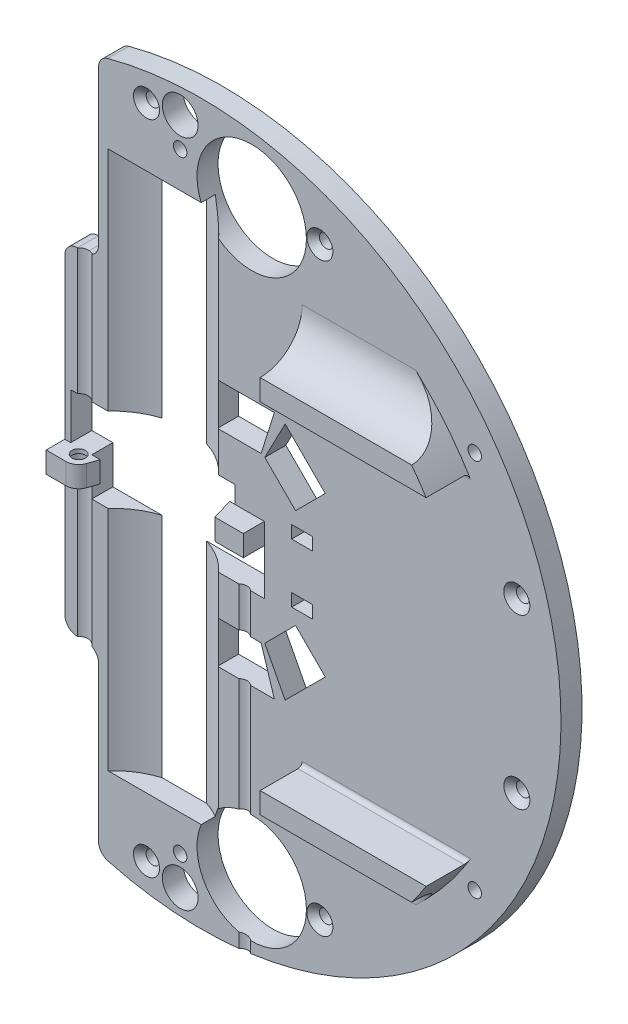
SolidWorks part; units mm, degrees
ref_plane "Front Plane" through (0, 0, 0) normal (1, 0, 0) x (0, 1, 0)
ref_plane "Top Plane" through (0, 0, 0) normal (0, 0, 1) x (0, 1, 0)
ref_plane "Right Plane" through (0, 0, 0) normal (0, 1, 0) x (-1, 0, 0)
sketch "Sketch1" plane through (0, 0, 0) normal (0, 0, 1) x (0, 1, 0)
  line L0 (0, 0) -> (0, -81.5088) construction
  line L1 (-40, 24.3888) -> (-40, 32.4114)
  line L2 (-40, 32.4114) -> (40, 32.4114)
  line L6 (-81.9478, 24.3888) -> (-40, 24.3888)
  line L7 (81.941, 24.4114) -> (40, 24.4114)
  line L8 (40, 24.4114) -> (40, 32.4114)
  arc A0 (-81.9478, 24.3888) -> (81.941, 24.4114) centre (0, 0) ccw
  circle A1 centre (-20, -75) radius 1.6
  circle A2 centre (20, -75) radius 1.6
  circle A3 centre (-69.5, -28.2) radius 1.6
  circle A9 centre (-78, 13) radius 1.6
  circle A10 centre (-79.5, 5) radius 4.25
  circle A11 centre (-69, -12) radius 13
  circle A16 centre (69, -12) radius 13
  circle A17 centre (79.5, 5) radius 4.25
  circle A18 centre (78, 13) radius 1.6
  circle A19 centre (69.5, -28.2) radius 1.6
  dimension "D1" = 171
  dimension "D3" = 3.2
  dimension "D7" = 3.2
  dimension "D8" = 78
  dimension "D13" = 5
  dimension "D14" = 69
  dimension "D16" = 40
  dimension "D2" = 75
  dimension "D4" = 20
  dimension "D5" = 69.5
  dimension "D6" = 28.2
  dimension "D9" = 40
  dimension "D10" = 13
  dimension "D11" = 8
  dimension "D12" = 79.5
  dimension "D15" = 12
extrude "Boss-Extrude2" add sketch "Sketch1" along normal blind 5
sketch "Sketch2" plane through (0, 0, 5) normal (0, 0, 1) x (1, 0, 0)
  line L1 (60, 45) -> (24, 45)
  line L3 (63.4429, 40) -> (24, 40)
  line L4 (24, 45) -> (24, 40)
  line L6 (24, -45) -> (24, -40)
  line L7 (63.4429, -40) -> (24, -40)
  line L8 (60, -45) -> (24, -45)
  arc A3 (60, -45) -> (63.4429, -40) centre (0, 0) ccw
  arc A4 (63.4429, 40) -> (60, 45) centre (0, 0) ccw
  dimension "D1" = 150
  dimension "D2" = 40
extrude "Boss-Extrude3" add sketch "Sketch2" along normal blind 10
fillet "Fillet1" radius 10 2 edges at (42, -45, 5) (42, 45, 5)
fillet "Fillet2" radius 1 2 edges at (43.7214, -40, 5) (43.7214, 40, 5)
sketch "Sketch5" plane through (0, 0, 5) normal (0, 0, 1) x (1, 0, 0)
  line L0 (0, 0) -> (93.3614, 0) construction
  circle A0 centre (65, 45) radius 1.6
  circle A2 centre (-5, 72.5) radius 1.6
  circle A4 centre (65, -45) radius 1.6
  circle A5 centre (-5, -72.5) radius 1.6
  dimension "D1" = 3.2
  dimension "D5" = 3.2
  dimension "D2" = 65
  dimension "D3" = 45
  dimension "D4" = 5
  dimension "D6" = 72.5
extrude "Cut-Extrude2" cut sketch "Sketch5" against normal blind 10
chamfer "Chamfer1" distance 1.5 angle 45 6 edges at (-14.6, -78, 5) (29.8, -69.5, 5) (76.6, -20, 5) (73.4, 20, 5) (26.6, 69.5, 5) (-11.4, 78, 5)
chamfer "Chamfer2" distance 1.5 angle 45 4 edges at (-3.4, 72.5, 0) (-3.4, -72.5, 0) (66.6, -45, 0) (66.6, 45, 0)
sketch "Sketch9" plane through (0, 0, 5) normal (0, 0, 1) x (1, 0, 0)
  line L1 (17.112, -24.1831) -> (24.1831, -17.112) construction
  line L6 (14.2376, -19.4864) -> (3.8798, -19.4864)
  line L8 (15.1085, -19.1155) -> (22.4153, -11.8087)
  line L10 (22.4153, -11.8087) -> (29.4864, -18.8798)
  line L11 (19.9404, -28.4257) -> (29.4864, -18.8798)
  line L12 (11.8087, -22.4153) -> (29.4864, -18.8798) construction
  line L13 (22.4153, -11.8087) -> (18.8798, -29.4864) construction
  line L14 (0, 0) -> (90.6538, 0) construction
  line L23 (17.3798, -29.4864) -> (3.8798, -29.4864)
  line L24 (3.8798, -19.4864) -> (3.8798, -29.4864)
  line L25 (18.8798, -19.4864) -> (3.8798, -29.4864) construction
  line L26 (18.8798, -29.4864) -> (3.8798, -19.4864) construction
  line L32 (15.1085, -19.1155) -> (19.9404, -28.4257)
  line L33 (17.3798, -29.4864) -> (14.2376, -19.4864)
  line L34 (17.3798, 29.4864) -> (14.2376, 19.4864)
  line L35 (14.2376, 19.4864) -> (3.8798, 19.4864)
  line L36 (3.8798, 19.4864) -> (3.8798, 29.4864)
  line L37 (17.3798, 29.4864) -> (3.8798, 29.4864)
  line L38 (15.1085, 19.1155) -> (19.9404, 28.4257)
  line L39 (15.1085, 19.1155) -> (22.4153, 11.8087)
  line L40 (22.4153, 11.8087) -> (29.4864, 18.8798)
  line L41 (19.9404, 28.4257) -> (29.4864, 18.8798)
  point P1 (11.3798, -24.4864)
  point P6 (20.6475, -20.6475)
  dimension "D1" = 10
  dimension "D2" = 15
  dimension "D3" = 15
  dimension "D4" = 10
  dimension "D6" = 1.5
  dimension "D7" = 1.5
extrude "Cut-Extrude3" cut sketch "Sketch9" against normal blind 10
sketch "Sketch10" plane through (0, 0, 0) normal (0, 1, 0) x (-1, 0, 0)
  line L0 (-85.5, 0) -> (24.4114, 0) construction
  circle A0 centre (9, 17) radius 17.8
  dimension "D1" = 35.6
  dimension "D2" = 17
  dimension "D3" = 9
extrude "Cut-Extrude4" cut sketch "Sketch10" against normal blind 64 and the other way blind 64
sketch "Sketch11" plane through (0, 0, 5) normal (0, 0, 1) x (1, 0, 0)
  line L0 (-26, -0.9) -> (-31, -0.9)
  line L1 (8, 10) -> (-25, 10)
  line L3 (15, -10) -> (-26, -10)
  line L4 (-26, -0.9) -> (-26, -10)
  line L5 (15, -10) -> (15, 0.9)
  line L6 (8, 10) -> (8, 0.9)
  line L7 (8, 0.9) -> (15, 0.9)
  line L8 (-31, -0.9) -> (-31, 10)
  line L9 (-31, 10) -> (-25, 10)
  point P0 (0, 0)
  dimension "D1" = 20
  dimension "D2" = 10
  dimension "D3" = 6
  dimension "D4" = 15
  dimension "D5" = 7
  dimension "D6" = 0.9
  dimension "D7" = 0.9
  dimension "D8" = 5
extrude "Cut-Extrude5" cut sketch "Sketch11" against normal blind 62.5
sketch "Sketch12" plane through (0, 0, 5) normal (0, 0, 1) x (1, 0, 0)
  line L1 (10.2402, 0) -> (10.2402, 0.9) construction
  line L2 (-6.5732, 0) -> (-6.5732, 0.9) construction
  line L3 (-6.5732, 0.9) -> (10.2402, 0.9) construction
  line L4 (-16.3028, 0) -> (-16.3028, -0.9) construction
  line L5 (-8.6264, 0) -> (-8.6264, -0.9) construction
  dimension "D1" = 0.9
  dimension "D2" = 0.9
ref_plane "Plane2" through (0, 0.9, 0) normal (0, -1, 0) x (1, 0, 0)
sketch "Sketch13" plane through (0, 0, 5) normal (0, 0, 1) x (1, 0, 0)
  line L0 (-6.5732, 0.9) -> (10.2402, 0.9) construction
  line L1 (15, 0.9) -> (6.7929, 0.9)
  line L2 (15, 0.9) -> (15, 5.9)
  line L3 (15, 5.9) -> (6.7929, 5.9)
  line L4 (6.7929, 0.9) -> (6.7929, 5.9)
  dimension "D1" = 5
extrude "Boss-Extrude4" add sketch "Sketch13" along normal blind 5
sketch "Sketch14" plane through (0, 0.9, 0) normal (0, -1, 0) x (1, 0, 0)
  circle A1 centre (10.3299, 6.4392) radius 2
  dimension "D2" = 4
extrude "Cut-Extrude6" cut sketch "Sketch14" against normal blind 4 and the other way blind 110
sketch "Sketch15" plane through (0, 0.9, 0) normal (0, -1, 0) x (1, 0, 0)
  line L2 (6.7929, 5) -> (6.7929, 10)
  line L3 (6.7929, 10) -> (8.2341, 10)
  line L4 (6.7929, 5) -> (8.2341, 10)
extrude "Cut-Extrude7" cut sketch "Sketch15" against normal blind 15
sketch "Sketch16" plane through (0, 0, 5) normal (0, 0, 1) x (1, 0, 0)
  line L0 (-32.4114, 40) -> (-32.4114, -40) construction
  line L1 (-32.4114, -0.9) -> (-24, -0.9)
  line L2 (-32.4114, -0.9) -> (-32.4114, -5.9)
  line L3 (-32.4114, -5.9) -> (-24, -5.9)
  line L4 (-24, -0.9) -> (-24, -5.9)
  dimension "D1" = 5
extrude "Boss-Extrude5" add sketch "Sketch16" along normal blind 5
sketch "Sketch17" plane through (0, -5.9, 0) normal (0, -1, 0) x (1, 0, 0)
  circle A0 centre (-27.6683, 6.4392) radius 2.25
  dimension "D1" = 4.5
extrude "Cut-Extrude8" cut sketch "Sketch17" against normal blind 4 and the other way blind 40
sketch "Sketch18" plane through (0, -5.9, 0) normal (0, -1, 0) x (1, 0, 0)
  line L0 (-24, 5) -> (-24.8314, 7.4156)
  line L1 (-32.4114, 10) -> (-24, 10) construction
  line L2 (-25.7209, 10) -> (-24, 10)
  line L3 (-24, 10) -> (-24, 5)
  line L5 (-27.6683, 9.4394) -> (-32.4114, 9.4394)
  line L6 (-32.4114, 10) -> (-32.4114, 5) construction
  line L7 (-32.4114, 9.4394) -> (-32.4114, 10)
  line L8 (-32.4114, 10) -> (-25.7209, 10)
  arc A1 (-24.8314, 7.4156) -> (-27.6683, 9.4394) centre (-27.6683, 6.4392) ccw
extrude "Cut-Extrude9" cut sketch "Sketch18" against normal blind 7
sketch "Sketch19" plane through (0, -1.9, 0) normal (0, -1, 0) x (1, 0, 0)
  circle A0 centre (-27.6683, 6.4392) radius 1.6
  dimension "D1" = 3.2
extrude "Cut-Extrude10" cut sketch "Sketch19" against normal blind 7
sketch "Sketch20" plane through (0, -0.9, 0) normal (0, 1, 0) x (-1, 0, 0)
  circle A0 centre (27.6683, 6.4392) radius 2.25
  dimension "D1" = 4.5
extrude "Cut-Extrude11" cut sketch "Sketch20" along normal blind 45
sketch "Sketch21" plane through (0, 0, 0) normal (0, 0, -1) x (1, 0, 0)
  line L1 (69.738, 4) -> (6.369, 4)
  line L2 (69.738, 4) -> (69.738, -4)
  line L3 (69.738, -4) -> (6.369, -4)
  line L4 (6.369, 4) -> (6.369, -4)
  dimension "D1" = 8
  dimension "D2" = 4
extrude "Cut-Extrude12" cut sketch "Sketch21" against normal blind 3
sketch "Sketch22" plane through (0, 0, 0) normal (0, 0, -1) x (1, 0, 0)
  line L0 (0, 0) -> (46.1564, 0) construction
  line L1 (21.5, -5.5) -> (26.5, -5.5)
  line L2 (21.5, -5.5) -> (21.5, -8.5)
  line L3 (21.5, -8.5) -> (26.5, -8.5)
  line L4 (26.5, -5.5) -> (26.5, -8.5)
  line L5 (21.5, -5.5) -> (26.5, -8.5) construction
  line L6 (21.5, -8.5) -> (26.5, -5.5) construction
  line L11 (21.5, 8.5) -> (26.5, 5.5) construction
  line L12 (21.5, 5.5) -> (26.5, 8.5) construction
  line L13 (26.5, 5.5) -> (26.5, 8.5)
  line L14 (21.5, 8.5) -> (26.5, 8.5)
  line L15 (21.5, 5.5) -> (21.5, 8.5)
  line L16 (21.5, 5.5) -> (26.5, 5.5)
  point P0 (24, -7)
  point P12 (24, 7)
  dimension "D1" = 5
  dimension "D2" = 3
  dimension "D3" = 7
  dimension "D4" = 24
extrude "Cut-Extrude13" cut sketch "Sketch22" against normal blind 5
sketch "Sketch23" plane through (0, 0, 5) normal (0, 0, 1) x (1, 0, 0)
fillet "Fillet3" radius 3 6 edges at (-24.3888, -40, 2.5) (-32.4114, -40, 2.5) (-24.4114, 40, 2.5) (-32.4114, 40, 2.5) (-24.4114, 81.941, 2.5) (-24.3888, -81.9478, 2.5)
